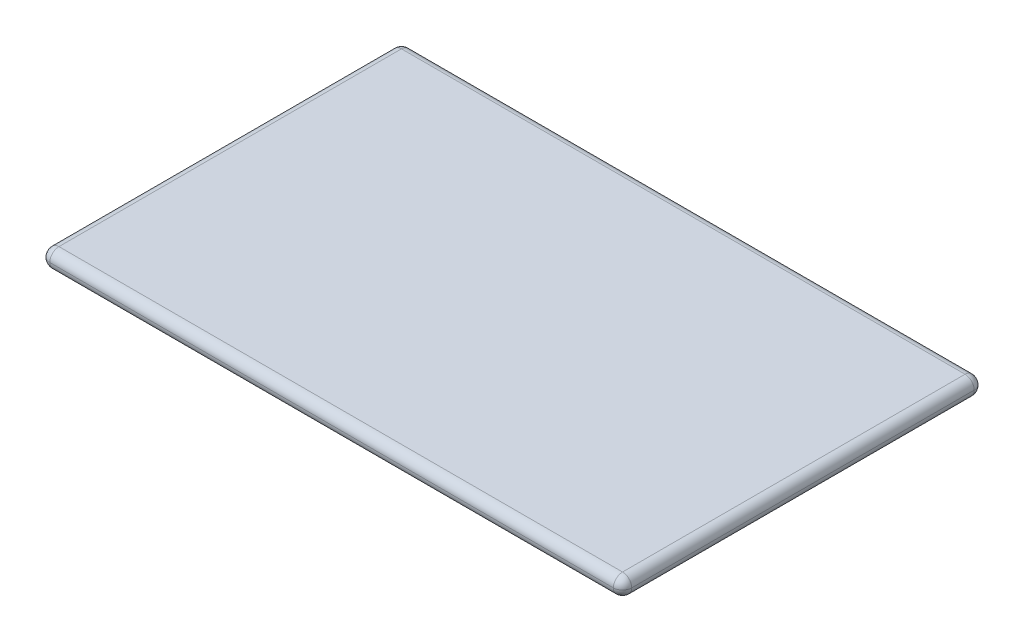
SolidWorks part; units mm, degrees
material "Plain Carbon Steel"
ref_plane "Front Plane" through (0, 0, 0) normal (0, 0, 1) x (1, 0, 0)
ref_plane "Top Plane" through (0, 0, 0) normal (0, 1, 0) x (1, 0, 0)
ref_plane "Right Plane" through (0, 0, 0) normal (1, 0, 0) x (0, 0, -1)
sketch "Sketch1" plane through (0, 0, 0) normal (0, 0, 1) x (1, 0, 0)
  line L1 (-6.4516, 0.2032) -> (6.4516, 0.2032)
  line L2 (-6.4516, 0.2032) -> (-6.4516, -0.2032)
  line L3 (-6.4516, -0.2032) -> (6.4516, -0.2032)
  line L4 (6.4516, 0.2032) -> (6.4516, -0.2032)
  line L5 (-6.4516, 0.2032) -> (6.4516, -0.2032) construction
  line L6 (-6.4516, -0.2032) -> (6.4516, 0.2032) construction
  line L9 (-6.0452, -0.2032) -> (-6.4516, -0.2032)
  line L16 (6.0452, -0.2032) -> (6.4516, -0.2032)
  point P0 (0, 0)
  dimension "D1" = 0.4064
  dimension "D2" = 12.9032
extrude "Boss-Extrude1" add sketch "Sketch1" along normal mid plane 8.001 contours L4 L1 L2 L3 | L3 | L3 region at (0, 0, 0)
fillet "Fillet3" radius 0.2032 12 edges at (0, -0.2032, -4.0005) (0, 0.2032, -4.0005) (0, -0.2032, 4.0005) (0, 0.2032, 4.0005) (-6.4516, 0, -4.0005) (6.4516, 0, -4.0005) (-6.4516, 0, 4.0005) (6.4516, 0, 4.0005) (6.4516, -0.2032, 0) (6.4516, 0.2032, 0) (-6.4516, 0.2032, 0) (-6.4516, -0.2032, 0)
